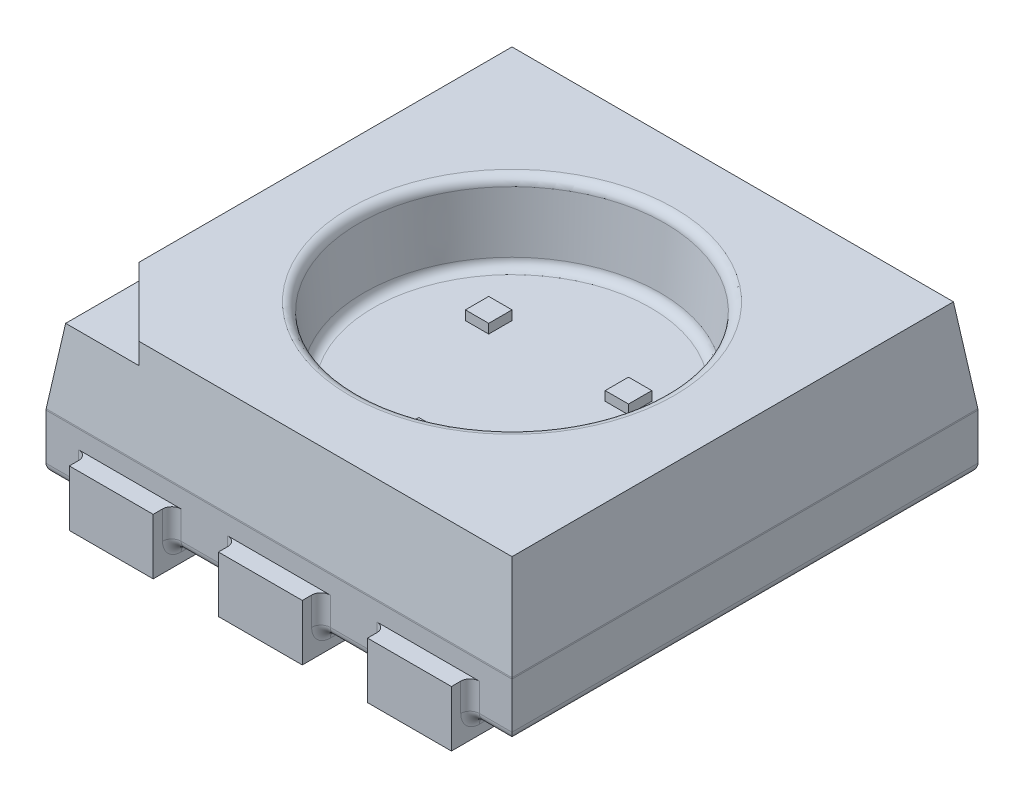
SolidWorks part; units mm, degrees
ref_plane "Front Plane" through (0, 0, 0) normal (0, 0, 1) x (1, 0, 0)
ref_plane "Top Plane" through (0, 0, 0) normal (0, 1, 0) x (1, 0, 0)
ref_plane "Right Plane" through (0, 0, 0) normal (1, 0, 0) x (0, 0, -1)
sketch "Sketch1" plane through (0, 0, 0) normal (0, 1, 0) x (1, 0, 0)
  line L1 (-2.5, 2.5) -> (2.5, 2.5)
  line L2 (-2.5, 2.5) -> (-2.5, -2.5)
  line L3 (-2.5, -2.5) -> (2.5, -2.5)
  line L4 (2.5, 2.5) -> (2.5, -2.5)
  line L5 (-2.5, 2.5) -> (2.5, -2.5) construction
  line L6 (-2.5, -2.5) -> (2.5, 2.5) construction
  point P0 (0, 0)
  dimension "D1" = 5
extrude "Boss-Extrude1" add sketch "Sketch1" along normal mid plane 1.6
sketch "Sketch2" plane through (0, -0.8, 0) normal (0, -1, 0) x (1, 0, 0)
  line L0 (0, 3.0343) -> (0, -3.2829) construction
  line L1 (-3.1068, 0) -> (2.8169, 0) construction
  line L2 (-2.5, 2.5) -> (2.5, 2.5) construction
  line L3 (-2.05, 2.7) -> (-1.15, 2.7)
  line L4 (-2.05, 2.7) -> (-2.05, 1.7)
  line L5 (-2.05, 1.7) -> (-1.15, 1.7)
  line L6 (-1.15, 2.7) -> (-1.15, 1.7)
  line L7 (-2.05, 2.7) -> (-1.15, 1.7) construction
  line L8 (-2.05, 1.7) -> (-1.15, 2.7) construction
  line L9 (2.05, 1.7) -> (1.15, 1.7)
  line L10 (-0.45, 2.7) -> (0.45, 2.7)
  line L11 (-0.45, 2.7) -> (-0.45, 1.7)
  line L12 (-0.45, 1.7) -> (0.45, 1.7)
  line L13 (0.45, 2.7) -> (0.45, 1.7)
  line L14 (-0.45, 2.7) -> (0.45, 1.7) construction
  line L15 (-0.45, 1.7) -> (0.45, 2.7) construction
  line L16 (1.15, 2.7) -> (1.15, 1.7)
  line L17 (2.05, 2.7) -> (1.15, 2.7)
  line L18 (2.05, 2.7) -> (2.05, 1.7)
  line L19 (2.05, -2.7) -> (2.05, -1.7)
  line L20 (2.05, -2.7) -> (1.15, -2.7)
  line L21 (1.15, -2.7) -> (1.15, -1.7)
  line L22 (2.05, -1.7) -> (1.15, -1.7)
  line L23 (-0.45, -1.7) -> (0.45, -1.7)
  line L24 (0.45, -2.7) -> (0.45, -1.7)
  line L25 (-0.45, -2.7) -> (0.45, -2.7)
  line L26 (-0.45, -2.7) -> (-0.45, -1.7)
  line L27 (-2.05, -1.7) -> (-1.15, -1.7)
  line L28 (-1.15, -2.7) -> (-1.15, -1.7)
  line L29 (-2.05, -2.7) -> (-1.15, -2.7)
  line L30 (-2.05, -2.7) -> (-2.05, -1.7)
  point P5 (-1.33, 2.5)
  point P12 (0, 2.2)
  point P21 (0, 0)
  point P22 (0, 0)
  point P23 (0, 0)
  point P24 (-1.6, 2.5)
  dimension "D1" = 0.9
  dimension "D2" = 2.3
  dimension "D3" = 4.1
  dimension "D4" = 3.4
  dimension "D5" = 5.4
extrude "Boss-Extrude2" add sketch "Sketch2" along normal blind 0.2 and the other way blind 0.4
chamfer "Chamfer1" distance 1 angle 7.5 4 edges at (0, 0.8, 2.5) (-2.5, 0.8, 0) (0, 0.8, -2.5) (2.5, 0.8, 0) first distance on face at (0, -0.45, 2.5) first distance on face at (-2.5, 0, 0) first distance on face at (0, -0.45, -2.5) first distance on face at (2.5, 0, 0)
sketch "Sketch3" plane through (0, 0.8, 0) normal (0, 1, 0) x (1, 0, 0)
  line L0 (-2.5, -1.5) -> (-1.5, -2.5)
  line L1 (-2.5, -2.5) -> (-2.5, 2.5) construction
  line L2 (2.5, -2.5) -> (-2.5, -2.5) construction
  line L3 (-1.5, -2.5) -> (-2.5, -2.5)
  line L4 (-2.5, -2.5) -> (-2.5, -1.5)
  dimension "D1" = 1
extrude "Cut-Extrude1" cut sketch "Sketch3" against normal blind 0.2
sketch "Sketch4" plane through (0, 0.8, 0) normal (0, 1, 0) x (1, 0, 0)
  circle A0 centre (0, 0) radius 1.65
  dimension "D1" = 3.3
extrude "Cut-Extrude2" cut sketch "Sketch4" against normal blind 0.8 draft 5
fillet "Fillet1" radius 0.1 46 edges at (-2.05, -0.6, 2.5) (-1.15, -0.6, 2.5) (-0.45, -0.6, 2.5) (0.45, -0.6, 2.5) (1.15, -0.6, 2.5) (2.05, -0.6, 2.5) (2.05, -0.6, -2.5) (1.15, -0.6, -2.5) (0.45, -0.6, -2.5) (-0.45, -0.6, -2.5) (-1.15, -0.6, -2.5) (-2.05, -0.6, -2.5) (-2.5, -0.8, 0) (-2.275, -0.8, 2.5) (-2.05, -0.8, 2.1) (-1.6, -0.8, 1.7) (-1.15, -0.8, 2.1) (-0.8, -0.8, 2.5) (-0.45, -0.8, 2.1) (0, -0.8, 1.7) (0.45, -0.8, 2.1) (0.8, -0.8, 2.5) (1.15, -0.8, 2.1) (1.6, -0.8, 1.7) (2.05, -0.8, 2.1) (2.275, -0.8, 2.5) (2.5, -0.8, 0) (2.275, -0.8, -2.5) (2.05, -0.8, -2.1) (1.6, -0.8, -1.7) (1.15, -0.8, -2.1) (0.8, -0.8, -2.5) (0.45, -0.8, -2.1) (0, -0.8, -1.7) (-0.45, -0.8, -2.1) (-0.8, -0.8, -2.5) (-1.15, -0.8, -2.1) (-1.6, -0.8, -1.7) (-2.05, -0.8, -2.1) (-2.275, -0.8, -2.5) (0, -0.2, -2.5) (2.5, -0.2, 0) (0, -0.2, 2.5) (-2.5, -0.2, 0) (0, 0.8, 1.65) (0, 0, 1.58)
sketch "Sketch5" plane through (0, 0, 0) normal (0, 1, 0) x (1, 0, 0)
  line L0 (0, 0) -> (0, 1.4884) construction
  line L1 (-0.875, 0.625) -> (-0.625, 0.625)
  line L2 (-0.875, 0.625) -> (-0.875, 0.375)
  line L3 (-0.875, 0.375) -> (-0.625, 0.375)
  line L4 (-0.625, 0.625) -> (-0.625, 0.375)
  line L5 (-0.875, 0.625) -> (-0.625, 0.375) construction
  line L6 (-0.875, 0.375) -> (-0.625, 0.625) construction
  line L7 (-0.125, -0.875) -> (0.125, -0.875)
  line L8 (-0.125, -0.875) -> (-0.125, -1.125)
  line L9 (-0.125, -1.125) -> (0.125, -1.125)
  line L10 (0.125, -0.875) -> (0.125, -1.125)
  line L11 (-0.125, -0.875) -> (0.125, -1.125) construction
  line L12 (-0.125, -1.125) -> (0.125, -0.875) construction
  line L17 (0.875, 0.375) -> (0.625, 0.625) construction
  line L18 (0.875, 0.625) -> (0.625, 0.375) construction
  line L19 (0.625, 0.625) -> (0.625, 0.375)
  line L20 (0.875, 0.375) -> (0.625, 0.375)
  line L21 (0.875, 0.625) -> (0.875, 0.375)
  line L22 (0.875, 0.625) -> (0.625, 0.625)
  circle A0 centre (0, 0) radius 1.4884 construction
  point P0 (-0.75, 0.5)
  point P5 (0, -1)
  point P14 (0.75, 0.5)
  point P21 (0, 0)
  point P22 (0.125, -0.7456)
  dimension "D1" = 1.5
  dimension "D2" = 0.25
  dimension "D3" = 1.5
  dimension "D4" = 0.5
extrude "Boss-Extrude4" add sketch "Sketch5" along normal blind 0.1 separate body
